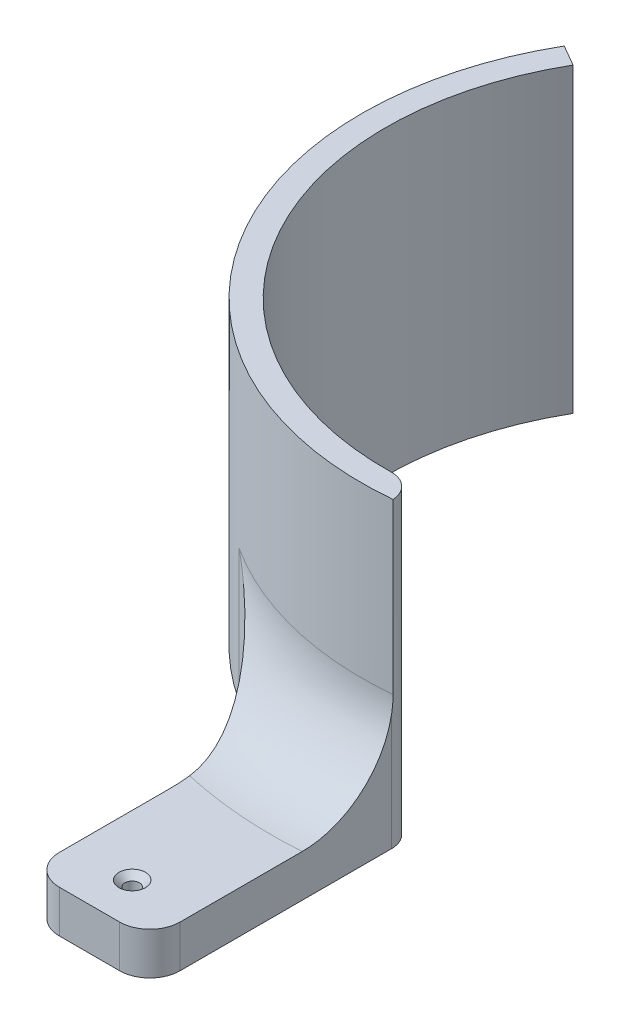
SolidWorks part; units mm, degrees
material "ABS"
ref_plane "Piano frontale" through (0, 0, 0) normal (0, 0, 1) x (1, 0, 0)
ref_plane "Piano superiore" through (0, 0, 0) normal (0, 1, 0) x (1, 0, 0)
ref_plane "Piano destro" through (0, 0, 0) normal (1, 0, 0) x (0, 0, -1)
sketch "Schizzo1" plane through (0, 0, 0) normal (0, 1, 0) x (1, 0, 0)
  line L0 (-45.8993, 26.5) -> (-42.4352, 24.5)
  line L2 (0, 0) -> (-42.4352, 24.5) construction
  line L3 (0, 0) -> (44.1673, 25.5) construction
  line L4 (0, 0) -> (0, 49.5002) construction
  line L5 (-15, -50.8331) -> (-15, -88.0749)
  line L6 (-10, -93.0749) -> (0, -93.0749)
  line L7 (5, -88.0749) -> (5, -52.7636)
  line L8 (0, -93.0749) -> (0, 0) construction
  line L9 (5, -52.7636) -> (5, -48.7442)
  arc A0 (-45.8993, 26.5) -> (5, -52.7636) centre (0, 0) ccw
  arc A1 (-42.4352, 24.5) -> (5, -48.7442) centre (0, 0) ccw
  arc A3 (5, -88.0749) -> (0, -93.0749) centre (0, -88.0749) cw
  arc A4 (-10, -93.0749) -> (-15, -88.0749) centre (-10, -88.0749) cw
  point P7 (0, 0)
  point P14 (5, -93.0749)
  point P17 (-15, -93.0749)
  point P18 (0, 0)
  point P20 (0, 24.5)
  point P21 (0, 49.5002)
  point P22 (0, 0)
  point P23 (0, 0)
  point P24 (0, 0)
  point P25 (0, 0)
  point P26 (0, 0)
  point P27 (0, 0)
  point P28 (5, -52.7636)
  point P29 (5, -88.0749)
  point P30 (0, 0)
  dimension "D1" = 106
  dimension "D2" = 4
  dimension "D5" = 20
  dimension "D7" = 5
  dimension "D3" = 120
  dimension "D4" = 60
  dimension "D6" = 93.0749
  dimension "D8" = 15
extrude "Estrusione-Estrusione1" add sketch "Schizzo1" along normal blind 50 contours A0 L0 A1 L9
ref_plane "Piano1" through (0, 0, -26.5) normal (0, 0, 1) x (1, 0, 0)
extrude "Estrusione-Estrusione2" add sketch "Schizzo1<3>" along normal blind 7 contours A0 L5 L6 L7 region at (-5.0797, 0, 72.4972)
sketch "Schizzo1<3>" plane through (0, 0, 0) normal (0, 1, 0) x (1, 0, 0) same geometry as "Schizzo1"
sketch "Schizzo2" plane through (0, 7, 0) normal (0, -1, 0) x (1, 0, 0)
  line L2 (-5, 86) -> (0, 86) construction
  line L3 (0, 86) -> (0, 0) construction
  point P0 (-5, 86)
  point P14 (-5, 86)
  dimension "D1" = 5
  dimension "D2" = 86
hole_wizard "Foro svasato per Vite M2-1" positions "Schizzo2" profile "Schizzo4" countersink size "M2" standard "ISO"
sketch "Schizzo4" plane through (-5, 7, 86) normal (1, 0, 0) x (0, 0, 1)
  line L0 (0, 0) -> (0, 12.661)
  line L1 (0, 12.661) -> (1.2, 11.94)
  line L2 (1.2, 11.94) -> (1.2, 1)
  line L3 (1.2, 1) -> (2.2, 0)
  line L5 (2.2, 0) -> (0, 0)
  line L6 (-1.2, 1) -> (-2.2, 0) construction
  line L10 (0, 12.661) -> (-1.2, 11.94) construction
  line L11 (0, -6.35) -> (0, 107.95) construction
  dimension "Hole Dia." = 2.4
  dimension "Hole Depth" = 11.94
  dimension "Near C'Sink Dia." = 4.4
  dimension "Near C'Sink Angle" = 90
  dimension "Drill Angle" = 118
fillet "Raccordo1" radius 30 1 edges at (-15, 3.5, 50.8331)
fillet "Raccordo2" radius 15 1 edges at (-12.5605, 7, 51.4901)
fillet "Raccordo3" radius 4 1 edges at (5, 25, 48.7442)
sketch "Schizzo5" plane through (0, 0, 0) normal (0, -1, 0) x (1, 0, 0)
  circle A0 centre (-5, 86) radius 2.9
  dimension "D1" = 5.8
extrude "Taglio-Estrusione1" cut sketch "Schizzo5" against normal blind 3
